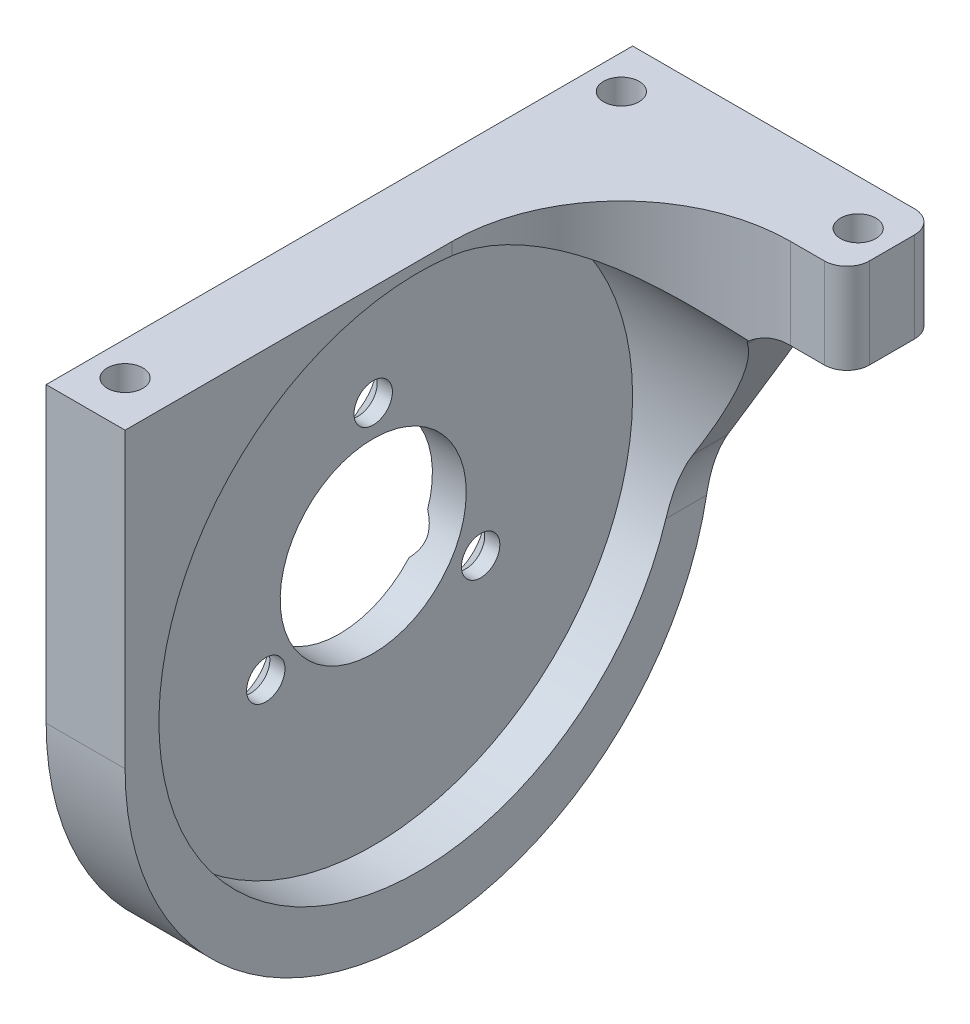
SolidWorks part; units mm, degrees
ref_plane "Plano frontal" through (0, 0, 0) normal (0, 0, 1) x (1, 0, 0)
ref_plane "Plano superior" through (0, 0, 0) normal (0, 1, 0) x (1, 0, 0)
ref_plane "Plano direito" through (0, 0, 0) normal (1, 0, 0) x (0, 0, -1)
sketch "Esboço1" plane through (0, 0, 0) normal (1, 0, 0) x (0, 0, -1)
  line L1 (0, 0) -> (52, 0)
  line L2 (0, 0) -> (0, 52)
  line L3 (0, 52) -> (52, 52)
  line L4 (52, 0) -> (52, 52)
  dimension "D1" = 52
  dimension "D2" = 52
extrude "Ressalto-extrusão1" add sketch "Esboço1" along normal blind 7
sketch "Esboço2" plane through (0, 0, 0) normal (-1, 0, 0) x (0, 0, 1)
  line L1 (-26, 52) -> (-26, 28.1)
  line L2 (-52, 52) -> (0, 52) construction
  circle A0 centre (-26, 28.1) radius 8.25
  dimension "D1" = 16.5
  dimension "D3" = 23.9
extrude "Corte-extrusão1" cut sketch "Esboço2" against normal through all contours A0
sketch "Esboço6" plane through (0, 0, 0) normal (-1, 0, 0) x (0, 0, 1)
  line L1 (-26, 52) -> (-26, 39.1)
  line L2 (-52, 52) -> (0, 52) construction
  circle A0 centre (-26, 28.1) radius 8.25 construction
  point P0 (-26, 39.1)
  dimension "D1" = 11
hole_wizard "Escareado para SFHCS M31" positions "Esboço13" profile "Esboço14" countersink size "M3" standard "Ansi Metric" end condition up to next
sketch "Esboço13" plane through (0, 0, 0) normal (-1, 0, 0) x (0, 0, 1)
  point P0 (-26, 39.1)
sketch "Esboço14" plane through (0, 39.1, -26) normal (0, 1, 0) x (0, 0, 1)
  line L0 (0, 0) -> (0, 7)
  line L1 (0, 7) -> (1.7, 7)
  line L2 (1.7, 7) -> (1.7, 1.66)
  line L3 (1.7, 1.66) -> (3.36, 0)
  line L5 (3.36, 0) -> (0, 0)
  line L6 (-1.7, 1.66) -> (-3.36, 0) construction
  line L11 (0, -6.35) -> (0, 107.95) construction
  dimension "Thru Hole Dia." = 3.4
  dimension "Thru Hole Depth" = 7
  dimension "Near C'Sink Dia." = 6.72
  dimension "Near C'Sink Angle" = 90
pattern_circular "PadrãoCircular1" count 3 over 360 about axis through (0, 28.1, -26) along (-1, 0, 0) of "Escareado para SFHCS M31"
sketch "Esboço27" plane through (7, 0, 0) normal (1, 0, 0) x (0, 0, -1)
  circle A0 centre (26, 28.1) radius 23
  dimension "D1" = 46
extrude "Corte-extrusão5" cut sketch "Esboço27" against normal blind 4
fillet "Filete1" radius 26 2 edges at (3.5, 0, -52) (3.5, 0, 0)
hole_wizard "Furo roscado para conduíte de M3x0.51" positions "Esboço33" profile "Esboço34" tap size "M3x0.5" standard "Helicoil® Metric"
sketch "Esboço33" plane through (0, 52, 0) normal (0, 1, 0) x (1, 0, 0)
  line L0 (0, 52) -> (0, 0) construction
  line L1 (7, 52) -> (0, 52) construction
  line L2 (7, 0) -> (0, 0) construction
  point P0 (3, 48)
  point P2 (3, 4)
  dimension "D1" = 3
  dimension "D2" = 4
  dimension "D3" = 3
  dimension "D4" = 4
cosmetic thread "Rosca de furo1"
cosmetic thread "Rosca de furo2"
sketch "Esboço34" plane through (3, 52, -48) normal (1, 0, 0) x (0, 0, 1)
  line L0 (0, 0) -> (0, 10.9464)
  line L1 (0, 10.9464) -> (1.575, 10)
  line L2 (1.575, 10) -> (1.575, 0)
  line L5 (1.575, 0) -> (0, 0)
  line L10 (0, 10.9464) -> (-1.575, 10) construction
  line L11 (0, -6.35) -> (0, 107.95) construction
  dimension "Tap Drill Dia." = 3.15
  dimension "Tap Drill Depth" = 10
  dimension "Drill Angle" = 118
sketch "Esboço35" plane through (0, 52, 0) normal (0, 1, 0) x (1, 0, 0)
  line L1 (7, 52) -> (27, 52)
  line L2 (7, 52) -> (7, 0)
  line L3 (7, 0) -> (27, 0)
  line L4 (27, 52) -> (27, 0)
  dimension "D1" = 20
  dimension "D2" = 52
extrude "Ressalto-extrusão2" add sketch "Esboço35" against normal blind 8
sketch "Esboço37" plane through (7, 0, 0) normal (1, 0, 0) x (0, 0, -1)
  circle A0 centre (26, 28.1) radius 23
extrude "Corte-extrusão6" cut sketch "Esboço37" along normal through all
chamfer "Chanfro1" distance 12 distance2 20 2 edges at (7, 44, -47.3095) (7, 44, -4.6905) first distance on face at (17, 44, -47.3095) first distance on face at (17, 44, -4.6905)
fillet "Filete2" radius 10 2 edges at (7, 24, -1.7227) (7, 24, -50.2773)
fillet "Filete3" radius 5 2 edges at (19, 44, -4.6905) (19, 44, -47.3095)
ref_plane "Plano1" through (13.5, 0, 0) normal (-1, 0, 0) x (0, 0, 1)
mirror "Espelhar1" about plane through (13.5, 0, 0) normal (-1, 0, 0) of "Furo roscado para conduíte de M3x0.51"
cosmetic thread "Rosca de furo3"
cosmetic thread "Rosca de furo4"
sketch "Esboço39" plane through (0, 52, 0) normal (0, 1, 0) x (1, 0, 0)
  line L0 (7, 26) -> (27, 26) construction
  line L3 (27, 9.381) -> (27, 42.619) construction
  line L4 (7, 4.0499) -> (7, 47.9501) construction
  line L5 (27, 44) -> (7, 44)
  line L6 (27, 44) -> (27, 8)
  line L7 (27, 8) -> (7, 8)
  line L8 (7, 44) -> (7, 8)
  line L9 (27, 44) -> (7, 8) construction
  line L10 (27, 8) -> (7, 44) construction
  point P4 (17, 26)
  dimension "D1" = 36
extrude "Corte-extrusão7" cut sketch "Esboço39" against normal up to next
fillet "Filete5" radius 15 2 edges at (7, 47.2089, -44) (7, 47.2089, -8)
fillet "Filete6" radius 2 4 edges at (27, 48, -44) (27, 48, -52) (27, 48, -8) (27, 48, 0)
sketch "Esboço40" plane through (0, 0, 0) normal (0, 0, 1) x (1, 0, 0)
  line L1 (7, 0) -> (39.2437, 0)
  line L2 (7, 0) -> (7, 53.2303)
  line L3 (7, 53.2303) -> (39.2437, 53.2303)
  line L4 (39.2437, 0) -> (39.2437, 53.2303)
extrude "Corte-extrusão8" cut sketch "Esboço40" against normal up to next
